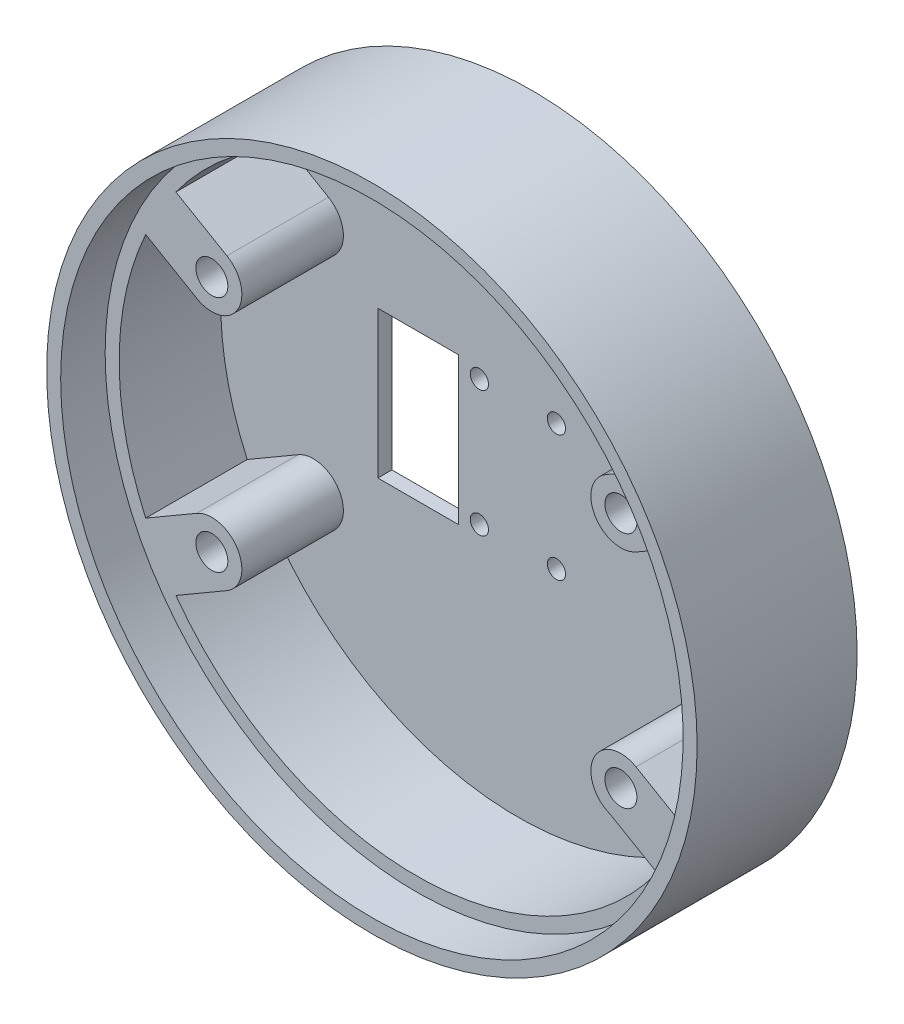
SolidWorks part; units mm, degrees
ref_plane "Front" through (0, 0, 0) normal (0, 0, 1) x (1, 0, 0)
ref_plane "Top" through (0, 0, 0) normal (0, 1, 0) x (1, 0, 0)
ref_plane "Right" through (0, 0, 0) normal (1, 0, 0) x (0, 0, -1)
sketch "Sketch1" plane through (0, 0, 0) normal (0, 0, 1) x (1, 0, 0)
  line L0 (0, -42.45) -> (0, 42.45) construction
  line L2 (-34.544, 0) -> (34.544, 0) construction
  circle A0 centre (0, 0) radius 42.45
  circle A7 centre (29.21, 17) radius 2.286
  circle A10 centre (29.21, -17) radius 2.286
  circle A11 centre (-29.21, -17) radius 2.286
  circle A12 centre (-29.21, 17) radius 2.286
  circle A13 centre (0, 0) radius 44.45
  circle A14 centre (0, 0) radius 46.45
  point P10 (0, 0)
  point P19 (-97.2534, 15.5778)
  dimension "D1" = 88.9
  dimension "D2" = 4.572
  dimension "D3" = 29.21
  dimension "D4" = 2
  dimension "D5" = 34
  dimension "D6" = 2
  dimension "D7" = 17
  dimension "D8" = 29.21
sketch "Sketch5" plane through (0, 0, 0) normal (0, 0, 1) x (1, 0, 0)
  line L0 (-34.544, 0) -> (34.544, 0) construction
  line L1 (0, 42.45) -> (0, -42.45) construction
  line L2 (-20.5, -11) -> (7.5, -11)
  line L3 (-20.5, -11) -> (-20.5, 11)
  line L4 (-20.5, 11) -> (7.5, 11)
  line L5 (7.5, -11) -> (7.5, 11)
  circle A0 centre (5.5, 9) radius 1.3
  circle A1 centre (-5.5, 9) radius 1.3
  circle A2 centre (-5.5, -9) radius 1.3
  circle A3 centre (5.5, -9) radius 1.3
  dimension "D1" = 2
  dimension "D2" = 2
  dimension "D3" = 28
  dimension "D4" = 22
extrude "Boss-Extrude5" add sketch "Sketch1" along normal blind 22.85 and the other way blind 0.0025 contours A14
extrude "Cut-Extrude13" cut sketch "Sketch1<12>" along normal through all contours A13
sketch "Sketch1<12>" plane through (0, 0, 0) normal (0, 0, 1) x (1, 0, 0) same geometry as "Sketch1"
hole_wizard "3/16 (0.1875) Dowel Hole1" positions "Sketch8" profile "Sketch9" hole size "3/16" standard "ANSI Inch" end condition through all
sketch "Sketch8" plane through (0, 0, 0) normal (0, 0, 1) x (1, 0, 0)
  point P0 (-29.21, 17)
sketch "Sketch9" plane through (-29.21, 17, 0) normal (1, 0, 0) x (0, -1, 0)
  line L0 (0, 0) -> (0, 0.0025)
  line L1 (0, 0.0025) -> (2.3812, 0.0025)
  line L2 (2.3812, 0.0025) -> (2.3812, 0)
  line L5 (2.3812, 0) -> (0, 0)
  line L11 (0, -6.35) -> (0, 107.95) construction
  dimension "Thru Hole Dia." = 4.7625
  dimension "Thru Hole Depth" = 0.0025
hole_wizard "3/16 (0.1875) Dowel Hole3" positions "Sketch12" profile "Sketch13" hole size "3/16" standard "ANSI Inch" end condition through all
sketch "Sketch12" plane through (0, 0, 0) normal (0, 0, 1) x (1, 0, 0)
  point P0 (-29.21, -17)
sketch "Sketch13" plane through (-29.21, -17, 0) normal (1, 0, 0) x (0, -1, 0)
  line L0 (0, 0) -> (0, 0.0025)
  line L1 (0, 0.0025) -> (2.3812, 0.0025)
  line L2 (2.3812, 0.0025) -> (2.3812, 0)
  line L5 (2.3812, 0) -> (0, 0)
  line L11 (0, -6.35) -> (0, 107.95) construction
  dimension "Thru Hole Dia." = 4.7625
  dimension "Thru Hole Depth" = 0.0025
hole_wizard "3/16 (0.1875) Dowel Hole4" positions "Sketch14" profile "Sketch15" hole size "3/16" standard "ANSI Inch" end condition through all
sketch "Sketch14" plane through (0, 0, 0) normal (0, 0, 1) x (1, 0, 0)
  point P0 (29.21, -17)
sketch "Sketch15" plane through (29.21, -17, 0) normal (1, 0, 0) x (0, -1, 0)
  line L0 (0, 0) -> (0, 0.0025)
  line L1 (0, 0.0025) -> (2.3812, 0.0025)
  line L2 (2.3812, 0.0025) -> (2.3812, 0)
  line L5 (2.3812, 0) -> (0, 0)
  line L11 (0, -6.35) -> (0, 107.95) construction
  dimension "Thru Hole Dia." = 4.7625
  dimension "Thru Hole Depth" = 0.0025
hole_wizard "3/16 (0.1875) Dowel Hole5" positions "Sketch16" profile "Sketch17" hole size "3/16" standard "ANSI Inch" end condition through all
sketch "Sketch16" plane through (0, 0, 0) normal (0, 0, 1) x (1, 0, 0)
  point P0 (29.21, 17)
sketch "Sketch17" plane through (29.21, 17, 0) normal (1, 0, 0) x (0, -1, 0)
  line L0 (0, 0) -> (0, 0.0025)
  line L1 (0, 0.0025) -> (2.3812, 0.0025)
  line L2 (2.3812, 0.0025) -> (2.3812, 0)
  line L5 (2.3812, 0) -> (0, 0)
  line L11 (0, -6.35) -> (0, 107.95) construction
  dimension "Thru Hole Dia." = 4.7625
  dimension "Thru Hole Depth" = 0.0025
sketch "Sketch20" plane through (0, 0, 22.85) normal (0, 0, 1) x (1, 0, 0)
  circle A1 centre (0, 0) radius 44.45
  circle A3 centre (0, 0) radius 44.45
  circle A4 centre (0, 0) radius 41.45
extrude "Boss-Extrude16" add sketch "Sketch1<21>" along normal blind 16.5 contours A13 A0 region at (-43.1928, 0, 0)
sketch "Sketch1<21>" plane through (0, 0, 0) normal (0, 0, 1) x (1, 0, 0) same geometry as "Sketch1"
sketch "Sketch21" plane through (0, 0, 0) normal (0, 0, 1) x (1, 0, 0)
  line L0 (-5.5, 9) -> (5.5, 9) construction
  line L1 (5.5, 9) -> (5.5, -9) construction
  line L2 (5.5, -9) -> (-5.5, -9) construction
  line L3 (-5.5, -9) -> (-5.5, 9) construction
  line L9 (-2.3552, 8) -> (2.3552, 8)
  line L10 (-2.3552, 8) -> (-2.3552, 10)
  line L15 (-2.3552, 10) -> (2.3552, 10)
  line L16 (2.3552, 8) -> (2.3552, 10)
  line L21 (-2.3552, 8) -> (2.3552, 10) construction
  line L22 (-2.3552, 10) -> (2.3552, 8) construction
  line L26 (4.5, 5.8552) -> (6.5, 5.8552)
  line L27 (4.5, 5.8552) -> (4.5, -5.8552)
  line L28 (4.5, -5.8552) -> (6.5, -5.8552)
  line L29 (6.5, 5.8552) -> (6.5, -5.8552)
  line L30 (4.5, 5.8552) -> (6.5, -5.8552) construction
  line L31 (4.5, -5.8552) -> (6.5, 5.8552) construction
  line L32 (-2.3552, -10) -> (2.3552, -10)
  line L33 (-2.3552, -10) -> (-2.3552, -8)
  line L34 (-2.3552, -8) -> (2.3552, -8)
  line L35 (2.3552, -10) -> (2.3552, -8)
  line L36 (-2.3552, -10) -> (2.3552, -8) construction
  line L37 (-2.3552, -8) -> (2.3552, -10) construction
  line L38 (-6.5, -5.8552) -> (-4.5, -5.8552)
  line L39 (-6.5, -5.8552) -> (-6.5, 5.8552)
  line L40 (-6.5, 5.8552) -> (-4.5, 5.8552)
  line L41 (-4.5, -5.8552) -> (-4.5, 5.8552)
  line L42 (-6.5, -5.8552) -> (-4.5, 5.8552) construction
  line L43 (-6.5, 5.8552) -> (-4.5, -5.8552) construction
  line L44 (7.5, -11) -> (-20.5, -11)
  line L45 (7.5, -11) -> (7.5, 11)
  line L46 (7.5, 11) -> (-20.5, 11)
  line L47 (-20.5, -11) -> (-20.5, 11)
  line L48 (-8.5, -10.5) -> (-20, -10.5)
  line L49 (-8.5, -10.5) -> (-8.5, 10.5)
  line L50 (-8.5, 10.5) -> (-20, 10.5)
  line L51 (-20, -10.5) -> (-20, 10.5)
  circle A4 centre (-5.5, 9) radius 1.3
  circle A5 centre (5.5, 9) radius 1.3
  circle A6 centre (5.5, -9) radius 1.3
  circle A7 centre (-5.5, -9) radius 1.3
  circle A8 centre (-5.5, -9) radius 3.3
  circle A9 centre (5.5, -9) radius 3.3
  circle A10 centre (-5.5, 9) radius 3.3
  circle A11 centre (5.5, 9) radius 3.3
  point P1 (0, 9)
  point P12 (0, 9)
  point P17 (5.5, 0)
  point P22 (0, -9)
  point P23 (0, -9)
  point P29 (-5.5, 0)
  point P33 (-5.5, 0)
  dimension "D5" = 2
  dimension "D1" = 2
  dimension "D2" = 2
  dimension "D3" = 2
  dimension "D4" = 2
  dimension "D6" = 22
  dimension "D7" = 28
  dimension "D8" = 2
  dimension "D9" = 2
  dimension "D10" = 3
  dimension "D11" = 0.5
  dimension "D12" = 0.5
  dimension "D13" = 0.5
sketch "Sketch24" plane through (0, 0, 0) normal (0, 0, 1) x (1, 0, 0)
  line L0 (-29.21, -17) -> (-38.4174, -22.3586) construction
  line L5 (29.21, 17) -> (38.4174, 22.3586) construction
  line L6 (-29.21, 17) -> (-38.4174, 22.3586) construction
  line L11 (29.21, -17) -> (38.4174, -22.3586) construction
  line L12 (29.21, 17) -> (27.0541, 20.7043) construction
  line L13 (27.0541, 20.7043) -> (31.3659, 13.2957) construction
  line L14 (40.5811, 18.6409) -> (31.3737, 13.2823)
  line L15 (40.5811, 18.6409) -> (36.2615, 26.0629)
  line L16 (31.3737, 13.2823) -> (27.0541, 20.7043)
  line L17 (36.2615, 26.0629) -> (27.0541, 20.7043)
  line L18 (29.2139, 16.9933) -> (38.4213, 22.3519) construction
  line L19 (35.9774, 15.9616) -> (31.6578, 23.3836) construction
  line L20 (27.0541, -20.7043) -> (29.21, -17) construction
  line L21 (29.21, -17) -> (31.3659, -13.2957) construction
  line L22 (-27.0541, -20.7043) -> (-31.3659, -13.2957) construction
  line L24 (-31.3659, 13.2957) -> (-29.21, 17) construction
  line L25 (-29.21, 17) -> (-27.0541, 20.7043) construction
  line L27 (36.2938, -26.0075) -> (27.0864, -20.6488)
  line L28 (36.2938, -26.0075) -> (40.5733, -18.6543)
  line L29 (27.0864, -20.6488) -> (31.3659, -13.2957)
  line L30 (40.5733, -18.6543) -> (31.3659, -13.2957)
  line L31 (29.2261, -16.9723) -> (38.4335, -22.3309) construction
  line L32 (31.6901, -23.3281) -> (35.9696, -15.975) construction
  line L33 (-36.2615, -26.0629) -> (-27.0541, -20.7043)
  line L34 (-36.2615, -26.0629) -> (-40.5733, -18.6543)
  line L35 (-27.0541, -20.7043) -> (-31.3659, -13.2957)
  line L36 (-40.5733, -18.6543) -> (-31.3659, -13.2957)
  line L37 (-29.21, -17) -> (-38.4174, -22.3586) construction
  line L38 (-31.6578, -23.3836) -> (-35.9696, -15.975) construction
  line L39 (-40.5733, 18.6543) -> (-31.3659, 13.2957)
  line L40 (-40.5733, 18.6543) -> (-36.2615, 26.0629)
  line L41 (-31.3659, 13.2957) -> (-27.0541, 20.7043)
  line L42 (-36.2615, 26.0629) -> (-27.0541, 20.7043)
  line L43 (-29.21, 17) -> (-38.4174, 22.3586) construction
  line L44 (-35.9696, 15.975) -> (-31.6578, 23.3836) construction
  circle A0 centre (29.21, 17) radius 4.286
  circle A1 centre (29.21, 17) radius 2.286 construction
  circle A3 centre (29.21, 17) radius 2.286
  circle A4 centre (29.21, -17) radius 4.286
  circle A5 centre (29.21, -17) radius 2.286
  circle A6 centre (-29.21, 17) radius 4.286
  circle A7 centre (-29.21, 17) radius 2.286
  circle A8 centre (-29.21, -17) radius 4.286
  circle A9 centre (-29.21, -17) radius 2.286
  circle A11 centre (0, 0) radius 44.45
  point P24 (33.8176, 19.6726)
  point P33 (33.8298, -19.6516)
  point P34 (-33.8137, -19.6793)
  point P37 (-33.8137, 19.6793)
  dimension "D1" = 2
  dimension "D2" = 90
  dimension "D3" = 90
  dimension "D4" = 90
  dimension "D5" = 90
extrude "Boss-Extrude15" add sketch "Sketch24" along normal blind 16.5 contours L14 A11 L17 A0 L16 | A0 | A6 | A8 | A4 | L14 L15 L17 L16 | L42 L41 L39 L40 | L36 L35 L33 L34 | L27 L29 L30 L28 region at (35.1858, 20.4649, 0)
extrude "Cut-Extrude21" cut sketch "Sketch24<4>" along normal through all and the other way blind 4 contours A3 | A5 | A9 | A7
sketch "Sketch24<4>" plane through (0, 0, 0) normal (0, 0, 1) x (1, 0, 0) same geometry as "Sketch24"
sketch "Sketch25" plane through (0, 0, 0) normal (0, 0, 1) x (1, 0, 0)
  circle A0 centre (0, 0) radius 42.45
extrude "Boss-Extrude17" add sketch "Sketch25" along normal blind 2
extrude "Cut-Extrude22" cut sketch "Sketch21" along normal through all both and the other way through all contours A4 | A5 | A6 | A7 | L48 L51 L50 L49 region at (-5.5, 9, 0)
sketch "Sketch26" plane through (0, 0, -0.0025) normal (0, 0, -1) x (-1, 0, 0)
  circle A0 centre (29.21, -17) radius 2.3813
  circle A1 centre (29.21, 17) radius 2.3813
  circle A2 centre (-29.21, 17) radius 2.3812
  circle A3 centre (-29.21, -17) radius 2.3812
extrude "Cut-Extrude23" cut sketch "Sketch26" against normal blind 3
equation "\"D1@Boss-Extrude5\"=0.25in+7mm+2.5mm+2mm+3mm+2mm"
equation "\"D1@Boss-Extrude16\"=7mm+2.5mm+2mm+3mm+2mm"
equation "\"D1@Boss-Extrude15\"=7mm+2.5MM+2mm+3mm+2mm"
